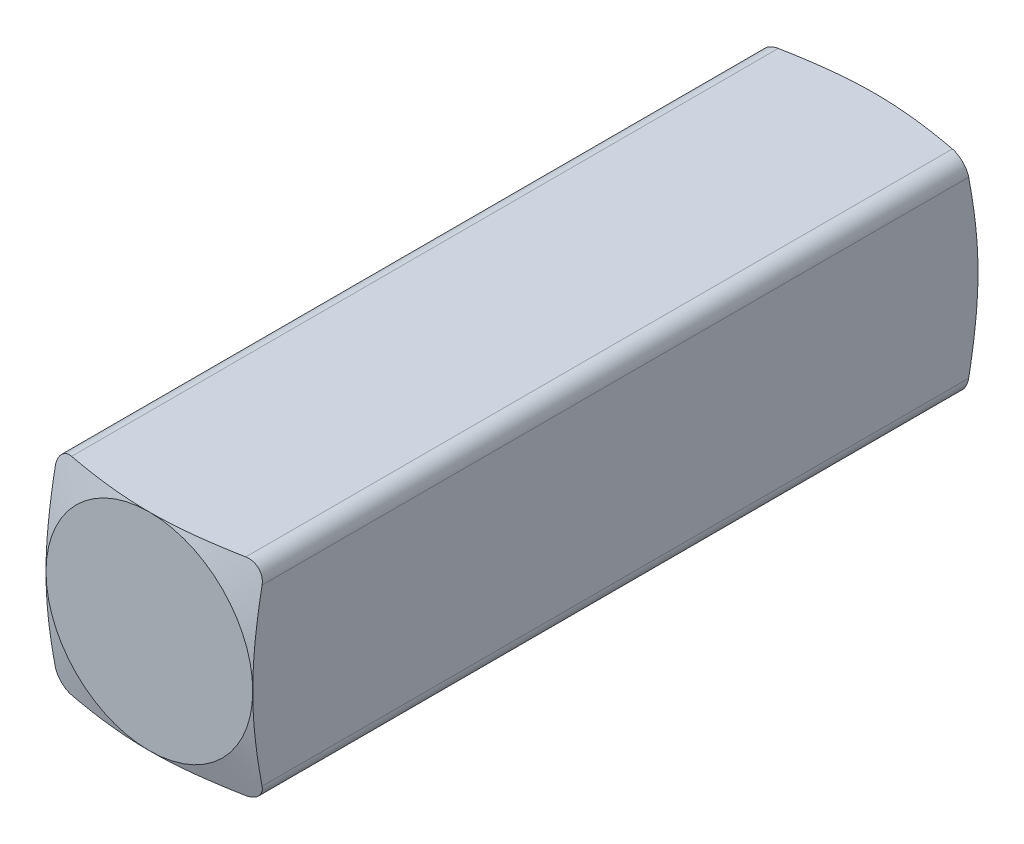
SolidWorks part; units mm, degrees
material "Plain Carbon Steel"
ref_plane "Front Plane" through (0, 0, 0) normal (0, 0, 1) x (1, 0, 0)
ref_plane "Top Plane" through (0, 0, 0) normal (0, 1, 0) x (1, 0, 0)
ref_plane "Right Plane" through (0, 0, 0) normal (1, 0, 0) x (0, 0, -1)
sketch "Sketch1" plane through (0, 0, 0) normal (0, 0, 1) x (1, 0, 0)
  line L0 (0.0501, 1.585) -> (0.0501, -1.585) construction
  line L1 (-1.5349, -1.585) -> (1.6351, -1.585)
  line L2 (-1.5349, -1.585) -> (-1.5349, 1.585)
  line L3 (-1.5349, 1.585) -> (1.6351, 1.585)
  line L4 (1.6351, -1.585) -> (1.6351, 1.585)
  line L5 (1.6351, 0) -> (-1.5349, 0) construction
  dimension "D1" = 3.17
  dimension "D2" = 3.17
  dimension "D3" = 1.6351
extrude "Extrude1" add sketch "Sketch1" along normal mid plane 11.12
sketch "Sketch4" plane through (0, 0, 0) normal (0, -1, 0) x (1, 0, 0)
  line L0 (1.6351, 5.56) -> (2.5551, 5.56)
  line L2 (2.5551, 5.56) -> (2.5551, 5.29)
  line L5 (0.0501, -5.56) -> (0.0501, 2.4929) construction
  line L6 (-1.5349, -5.56) -> (1.6351, -5.56) construction
  line L7 (1.6351, 11.0508) -> (1.6351, 10.1958) construction
  line L8 (2.5551, 5.29) -> (1.6351, 5.56)
  dimension "D1" = 0.27
  dimension "D2" = 0.9588
revolve "Cut-Revolve3" cut sketch "Sketch4" angle 360 about L5
mirror "Mirror2" about plane through (0, 0, 0) normal (0, 0, 1) of "Cut-Revolve3"
fillet "Fillet1" radius 0.25 4 edges at (1.6351, 1.585, 0) (1.6351, -1.585, 0) (-1.5349, -1.585, 0) (-1.5349, 1.585, 0)
ref_axis "Axis1" through (0.0501, 0, -6.4626) along (0, 0, 1)
